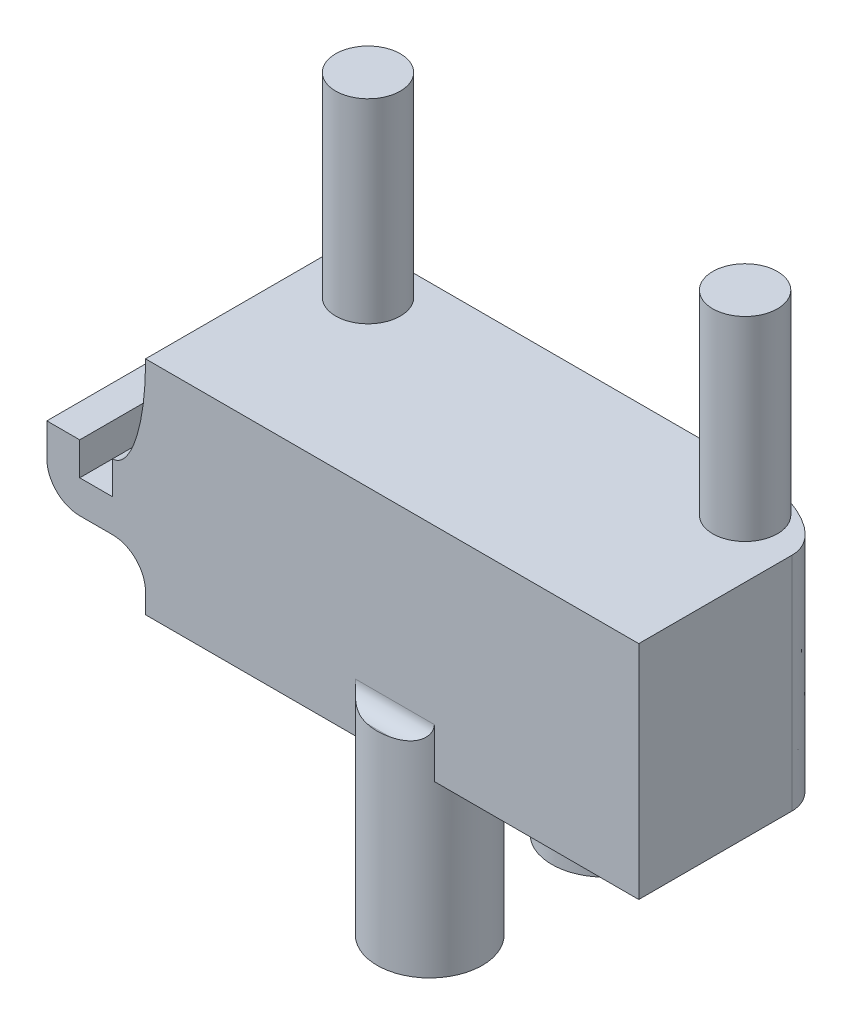
SolidWorks part; units mm, degrees
ref_plane "Front Plane" through (0, 0, 0) normal (0, 0, 1) x (1, 0, 0)
ref_plane "Top Plane" through (0, 0, 0) normal (0, 1, 0) x (1, 0, 0)
ref_plane "Right Plane" through (0, 0, 0) normal (1, 0, 0) x (0, 0, -1)
sketch "Sketch1" plane through (0, 0, 0) normal (0, 1, 0) x (1, 0, 0)
  line L1 (-40.1858, -24.5795) -> (-17.6858, -24.5795)
  line L2 (-40.1858, -24.5795) -> (-40.1858, -17.5795)
  line L3 (-40.1858, -17.5795) -> (-17.6858, -17.5795)
  line L4 (-17.6858, -24.5795) -> (-17.6858, -17.5795)
  dimension "D1" = 22.5
  dimension "D2" = 7
extrude "Boss-Extrude1" add sketch "Sketch1" along normal blind 1.5
sketch "Sketch2" plane through (0, 1.5, 0) normal (0, 1, 0) x (1, 0, 0)
  line L0 (-17.6858, -24.5795) -> (-17.6858, -17.5795) construction
  line L2 (-40.1858, -24.5795) -> (-17.6858, -24.5795) construction
  circle A0 centre (-37.5358, -19.5795) radius 1.475
  circle A1 centre (-20.3358, -19.5795) radius 1.475
  dimension "D1" = 2.95
  dimension "D2" = 2.95
  dimension "D3" = 17.2
  dimension "D4" = 2.65
  dimension "D5" = 5
  dimension "D6" = 5
extrude "Boss-Extrude2" add sketch "Sketch2" along normal blind 11.5
sketch "Sketch4" plane through (0, 0, 0) normal (0, -1, 0) x (-1, 0, 0)
  line L0 (40.1858, -17.5795) -> (40.1858, -24.5795) construction
  line L1 (17.6858, -24.5795) -> (40.1858, -24.5795)
  line L2 (17.6858, -24.5795) -> (17.6858, -27.0795)
  line L3 (17.6858, -27.0795) -> (40.1858, -27.0795)
  line L4 (40.1858, -24.5795) -> (40.1858, -27.0795)
  line L6 (20.9358, -27.0795) -> (23.9358, -27.0795)
  line L7 (20.9358, -27.0795) -> (20.9358, -29.9823)
  line L8 (20.9358, -29.9823) -> (23.9358, -29.9823)
  line L9 (23.9358, -27.0795) -> (23.9358, -29.9823)
  line L10 (32.4358, -27.0795) -> (35.4358, -27.0795)
  line L11 (32.4358, -27.0795) -> (32.4358, -28.8632)
  line L12 (32.4358, -28.8632) -> (35.4358, -28.8632)
  line L13 (35.4358, -27.0795) -> (35.4358, -28.8632)
  line M13 (40.1858, -24.5795) -> (40.1858, -17.5795)
  line M14 (40.1858, -17.5795) -> (17.6858, -17.5795)
  line M15 (17.6858, -17.5795) -> (17.6858, -24.5795)
  line M16 (17.6858, -24.5795) -> (40.1858, -24.5795)
  dimension "D1" = 0
  dimension "D2" = 3.25
  dimension "D3" = 4.75
  dimension "D4" = 2.5
  dimension "D5" = 3
  dimension "D6" = 3
extrude "Boss-Extrude4" add sketch "Sketch4" along normal blind 6 and the other way blind 1.5 contours L4 L2 L3 M16 | M16 M13 M14 M15
sketch "Sketch8" plane through (0, 1.5, 0) normal (0, 1, 0) x (1, 0, 0)
  line L1 (-40.1858, -17.5795) -> (-17.6858, -17.5795)
  line L2 (-40.1858, -17.5795) -> (-40.1858, -27.0795)
  line L3 (-40.1858, -27.0795) -> (-17.6858, -27.0795)
  line L4 (-17.6858, -17.5795) -> (-17.6858, -27.0795)
extrude "Boss-Extrude7" add sketch "Sketch8" along normal blind 2.61
sketch "Sketch9" plane through (0, -6, 0) normal (0, -1, 0) x (-1, 0, 0)
  line L0 (17.6858, -17.5795) -> (17.6858, -27.0795) construction
  line L3 (17.6858, -27.0795) -> (40.1858, -27.0795) construction
  circle A0 centre (28.8108, -25.4895) radius 2.4
  circle A1 centre (28.8108, -17.5195) radius 2.4
  dimension "D1" = 11.125
  dimension "D2" = 11.125
  dimension "D3" = 4.8
  dimension "D4" = 4.8
  dimension "D5" = 1.59
  dimension "D6" = 7.97
extrude "Boss-Extrude8" add sketch "Sketch9" along normal blind 7.76 and the other way blind 1.5
sketch "Sketch15" plane through (-40.1858, 0, 0) normal (-1, 0, 0) x (0, 0, 1)
  line L0 (27.0795, 4.11) -> (27.0795, -6) construction
  line L1 (27.0795, -0.59) -> (17.5795, -0.59)
  line L2 (27.0795, -0.59) -> (27.0795, -3.59)
  line L3 (27.0795, -3.59) -> (17.5795, -3.59)
  line L4 (17.5795, -0.59) -> (17.5795, -3.59)
  line L5 (17.5795, 4.11) -> (17.5795, -6) construction
  line L6 (17.5795, 4.11) -> (27.0795, 4.11) construction
  dimension "D1" = 3
  dimension "D2" = 4.7
extrude "Boss-Extrude11" add sketch "Sketch15" along normal blind 4.5
sketch "Sketch16" plane through (0, -0.59, 0) normal (0, 1, 0) x (1, 0, 0)
  line L0 (-44.6858, -27.0795) -> (-40.1858, -27.0795) construction
  line L1 (-41.6858, -27.0795) -> (-43.1858, -27.0795)
  line L2 (-41.6858, -27.0795) -> (-41.6858, -17.5795)
  line L3 (-41.6858, -17.5795) -> (-43.1858, -17.5795)
  line L4 (-43.1858, -27.0795) -> (-43.1858, -17.5795)
  line L5 (-44.6858, -17.5795) -> (-40.1858, -17.5795) construction
  line L6 (-44.6858, -27.0795) -> (-44.6858, -17.5795) construction
  line L7 (-40.1858, -27.0795) -> (-40.1858, -17.5795) construction
  dimension "D1" = 1.5
  dimension "D2" = 1.5
extrude "Cut-Extrude3" cut sketch "Sketch16" against normal blind 1.5
fillet "Fillet1" radius 1.5 3 edges at (-40.1858, -0.59, 22.3295) (-40.9358, -0.59, 17.5795) (-40.9358, -0.59, 27.0795)
fillet "Fillet2" radius 1.5 1 edges at (-44.6858, -3.59, 22.3295)
fillet "Fillet3" radius 1.5 1 edges at (-40.1858, -3.59, 22.3295)
fillet "Fillet4" radius 2 1 edges at (-28.8108, -4.5, 17.5795)
fillet "Fillet5" radius 0.75 1 edges at (-28.8108, -4.5, 27.0795)
fillet "Fillet9" radius 5 3 edges at (-17.6858, -6, 22.3295) (-28.9358, 4.11, 17.5795) (-17.6858, -0.945, 17.5795)
